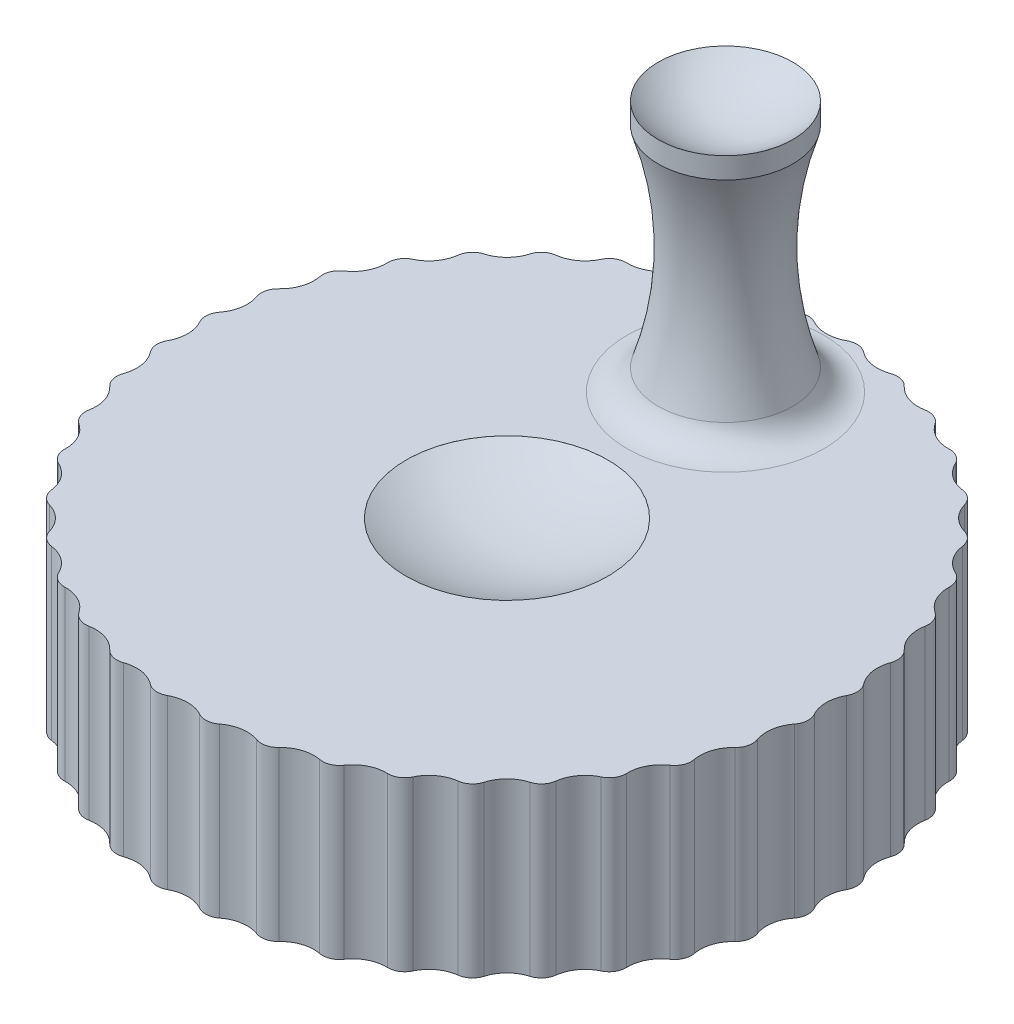
SolidWorks part; units mm, degrees
ref_plane "Front Plane" through (0, 0, 0) normal (0, 0, 1) x (1, 0, 0)
ref_plane "Top Plane" through (0, 0, 0) normal (0, 1, 0) x (1, 0, 0)
ref_plane "Right Plane" through (0, 0, 0) normal (1, 0, 0) x (0, 0, -1)
sketch "Sketch1" plane through (0, 0, 0) normal (0, 1, 0) x (1, 0, 0)
  circle A0 centre (0, 0) radius 20
  dimension "D1" = 40
extrude "Boss-Extrude1" add sketch "Sketch1" along normal blind 10
sketch "Sketch2" plane through (0, 10, 0) normal (0, 1, 0) x (1, 0, 0)
  arc A0 (-1.5536, 19.7405) -> (1.5536, 19.7405) centre (0, 21) ccw
  arc A1 (1.5536, 19.7405) -> (4.6226, 19.2544) centre (3.2851, 20.7415) ccw
  arc A2 (4.6226, 19.2544) -> (7.5777, 18.2943) centre (6.4894, 19.9722) ccw
  arc A3 (7.5777, 18.2943) -> (10.3463, 16.8836) centre (9.5338, 18.7111) ccw
  arc A4 (10.3463, 16.8836) -> (12.8601, 15.0572) centre (12.3435, 16.9894) ccw
  arc A5 (12.8601, 15.0572) -> (15.0572, 12.8601) centre (14.8492, 14.8492) ccw
  arc A6 (15.0572, 12.8601) -> (16.8836, 10.3463) centre (16.9894, 12.3435) ccw
  arc A7 (16.8836, 10.3463) -> (18.2943, 7.5777) centre (18.7111, 9.5338) ccw
  arc A8 (18.2943, 7.5777) -> (19.2544, 4.6226) centre (19.9722, 6.4894) ccw
  arc A9 (19.2544, 4.6226) -> (19.7405, 1.5536) centre (20.7415, 3.2851) ccw
  arc A10 (19.7405, 1.5536) -> (19.7405, -1.5536) centre (21, 0) ccw
  arc A11 (19.7405, -1.5536) -> (19.2544, -4.6226) centre (20.7415, -3.2851) ccw
  arc A12 (19.2544, -4.6226) -> (18.2943, -7.5777) centre (19.9722, -6.4894) ccw
  arc A13 (18.2943, -7.5777) -> (16.8836, -10.3463) centre (18.7111, -9.5338) ccw
  arc A14 (16.8836, -10.3463) -> (15.0572, -12.8601) centre (16.9894, -12.3435) ccw
  arc A15 (15.0572, -12.8601) -> (12.8601, -15.0572) centre (14.8492, -14.8492) ccw
  arc A16 (11.531, -18.8169) -> (14.3326, -16.7814) centre (12.3435, -16.9894) ccw
  arc A17 (8.4454, -20.3891) -> (11.531, -18.8169) centre (9.5338, -18.7111) ccw
  arc A18 (5.1519, -21.4592) -> (8.4454, -20.3891) centre (6.4894, -19.9722) ccw
  arc A19 (1.7315, -22.0009) -> (5.1519, -21.4592) centre (3.2851, -20.7415) ccw
  arc A20 (-1.7315, -22.0009) -> (1.7315, -22.0009) centre (0, -21) ccw
  arc A21 (-5.1519, -21.4592) -> (-1.7315, -22.0009) centre (-3.2851, -20.7415) ccw
  arc A22 (-8.4454, -20.3891) -> (-5.1519, -21.4592) centre (-6.4894, -19.9722) ccw
  arc A23 (-11.531, -18.8169) -> (-8.4454, -20.3891) centre (-9.5338, -18.7111) ccw
  arc A24 (-14.3326, -16.7814) -> (-11.531, -18.8169) centre (-12.3435, -16.9894) ccw
  arc A25 (-16.7814, -14.3326) -> (-14.3326, -16.7814) centre (-14.8492, -14.8492) ccw
  arc A26 (-18.8169, -11.531) -> (-16.7814, -14.3326) centre (-16.9894, -12.3435) ccw
  arc A27 (-20.3891, -8.4454) -> (-18.8169, -11.531) centre (-18.7111, -9.5338) ccw
  arc A28 (-21.4592, -5.1519) -> (-20.3891, -8.4454) centre (-19.9722, -6.4894) ccw
  arc A29 (-22.0009, -1.7315) -> (-21.4592, -5.1519) centre (-20.7415, -3.2851) ccw
  arc A30 (-22.0009, 1.7315) -> (-22.0009, -1.7315) centre (-21, 0) ccw
  arc A31 (-21.4592, 5.1519) -> (-22.0009, 1.7315) centre (-20.7415, 3.2851) ccw
  arc A32 (-20.3891, 8.4454) -> (-21.4592, 5.1519) centre (-19.9722, 6.4894) ccw
  arc A33 (-18.8169, 11.531) -> (-20.3891, 8.4454) centre (-18.7111, 9.5338) ccw
  arc A34 (-16.7814, 14.3326) -> (-18.8169, 11.531) centre (-16.9894, 12.3435) ccw
  arc A35 (-15.0572, 12.8601) -> (-12.8601, 15.0572) centre (-14.8492, 14.8492) ccw
  arc A36 (-12.8601, 15.0572) -> (-10.3463, 16.8836) centre (-12.3435, 16.9894) ccw
  arc A37 (-10.3463, 16.8836) -> (-7.5777, 18.2943) centre (-9.5338, 18.7111) ccw
  arc A38 (-7.5777, 18.2943) -> (-4.6226, 19.2544) centre (-6.4894, 19.9722) ccw
  arc A39 (-4.6226, 19.2544) -> (-1.5536, 19.7405) centre (-3.2851, 20.7415) ccw
  arc A40 (-14.3326, 16.7814) -> (-16.7814, 14.3326) centre (-14.8492, 14.8492) ccw
  arc A41 (-11.531, 18.8169) -> (-14.3326, 16.7814) centre (-12.3435, 16.9894) ccw
  arc A42 (-8.4454, 20.3891) -> (-11.531, 18.8169) centre (-9.5338, 18.7111) ccw
  arc A43 (-5.1519, 21.4592) -> (-8.4454, 20.3891) centre (-6.4894, 19.9722) ccw
  arc A44 (-1.7315, 22.0009) -> (-5.1519, 21.4592) centre (-3.2851, 20.7415) ccw
  arc A45 (1.7315, 22.0009) -> (-1.7315, 22.0009) centre (0, 21) ccw
  arc A46 (5.1519, 21.4592) -> (1.7315, 22.0009) centre (3.2851, 20.7415) ccw
  arc A47 (8.4454, 20.3891) -> (5.1519, 21.4592) centre (6.4894, 19.9722) ccw
  arc A48 (11.531, 18.8169) -> (8.4454, 20.3891) centre (9.5338, 18.7111) ccw
  arc A49 (14.3326, 16.7814) -> (11.531, 18.8169) centre (12.3435, 16.9894) ccw
  arc A50 (16.7814, 14.3326) -> (14.3326, 16.7814) centre (14.8492, 14.8492) ccw
  arc A51 (18.8169, 11.531) -> (16.7814, 14.3326) centre (16.9894, 12.3435) ccw
  arc A52 (20.3891, 8.4454) -> (18.8169, 11.531) centre (18.7111, 9.5338) ccw
  arc A53 (21.4592, 5.1519) -> (20.3891, 8.4454) centre (19.9722, 6.4894) ccw
  arc A54 (22.0009, 1.7315) -> (21.4592, 5.1519) centre (20.7415, 3.2851) ccw
  arc A55 (22.0009, -1.7315) -> (22.0009, 1.7315) centre (21, 0) ccw
  arc A56 (21.4592, -5.1519) -> (22.0009, -1.7315) centre (20.7415, -3.2851) ccw
  arc A57 (20.3891, -8.4454) -> (21.4592, -5.1519) centre (19.9722, -6.4894) ccw
  arc A58 (18.8169, -11.531) -> (20.3891, -8.4454) centre (18.7111, -9.5338) ccw
  arc A59 (16.7814, -14.3326) -> (18.8169, -11.531) centre (16.9894, -12.3435) ccw
  arc A60 (-16.8836, 10.3463) -> (-15.0572, 12.8601) centre (-16.9894, 12.3435) ccw
  arc A61 (-18.2943, 7.5777) -> (-16.8836, 10.3463) centre (-18.7111, 9.5338) ccw
  arc A62 (-19.2544, 4.6226) -> (-18.2943, 7.5777) centre (-19.9722, 6.4894) ccw
  arc A63 (-19.7405, 1.5536) -> (-19.2544, 4.6226) centre (-20.7415, 3.2851) ccw
  arc A64 (-19.7405, -1.5536) -> (-19.7405, 1.5536) centre (-21, 0) ccw
  arc A65 (-19.2544, -4.6226) -> (-19.7405, -1.5536) centre (-20.7415, -3.2851) ccw
  arc A66 (-18.2943, -7.5777) -> (-19.2544, -4.6226) centre (-19.9722, -6.4894) ccw
  arc A67 (-16.8836, -10.3463) -> (-18.2943, -7.5777) centre (-18.7111, -9.5338) ccw
  arc A68 (-15.0572, -12.8601) -> (-16.8836, -10.3463) centre (-16.9894, -12.3435) ccw
  arc A69 (-12.8601, -15.0572) -> (-15.0572, -12.8601) centre (-14.8492, -14.8492) ccw
  arc A70 (-10.3463, -16.8836) -> (-12.8601, -15.0572) centre (-12.3435, -16.9894) ccw
  arc A71 (-7.5777, -18.2943) -> (-10.3463, -16.8836) centre (-9.5338, -18.7111) ccw
  arc A72 (-4.6226, -19.2544) -> (-7.5777, -18.2943) centre (-6.4894, -19.9722) ccw
  arc A73 (-1.5536, -19.7405) -> (-4.6226, -19.2544) centre (-3.2851, -20.7415) ccw
  arc A74 (1.5536, -19.7405) -> (-1.5536, -19.7405) centre (0, -21) ccw
  arc A75 (4.6226, -19.2544) -> (1.5536, -19.7405) centre (3.2851, -20.7415) ccw
  arc A76 (7.5777, -18.2943) -> (4.6226, -19.2544) centre (6.4894, -19.9722) ccw
  arc A77 (10.3463, -16.8836) -> (7.5777, -18.2943) centre (9.5338, -18.7111) ccw
  arc A78 (14.3326, -16.7814) -> (16.7814, -14.3326) centre (14.8492, -14.8492) ccw
  arc A79 (12.8601, -15.0572) -> (10.3463, -16.8836) centre (12.3435, -16.9894) ccw
  point P64 (0, 0)
  dimension "D2" = 4
  dimension "D1" = 21
  dimension "D3" = 40
extrude "Cut-Extrude1" cut sketch "Sketch2" against normal through all both and the other way through all
fillet "Fillet2" radius 1 40 edges at (10.3463, 5, -16.8836) (7.5777, 5, -18.2943) (4.6226, 5, -19.2544) (1.5536, 5, -19.7405) (-1.5536, 5, -19.7405) (-4.6226, 5, -19.2544) (-7.5777, 5, -18.2943) (-12.8601, 5, -15.0572) (-15.0572, 5, -12.8601) (-16.8836, 5, -10.3463) (-18.2943, 5, -7.5777) (-19.2544, 5, -4.6226) (-19.7405, 5, -1.5536) (-19.7405, 5, 1.5536) (-19.2544, 5, 4.6226) (-16.8836, 5, 10.3463) (-15.0572, 5, 12.8601) (-12.8601, 5, 15.0572) (-7.5777, 5, 18.2943) (-1.5536, 5, 19.7405) (-4.6226, 5, 19.2544) (1.5536, 5, 19.7405) (4.6226, 5, 19.2544) (10.3463, 5, 16.8836) (12.8601, 5, 15.0572) (15.0572, 5, 12.8601) (16.8836, 5, 10.3463) (19.2544, 5, 4.6226) (19.7405, 5, -1.5536) (19.2544, 5, -4.6226) (18.2943, 5, -7.5777) (15.0572, 5, -12.8601)
sketch "Sketch4" plane through (0, 10, 0) normal (0, 1, 0) x (1, 0, 0)
  circle A0 centre (0, 0) radius 6
  dimension "D1" = 12
extrude "Cut-Extrude3" cut sketch "Sketch4" against normal blind 0.001
dome "Dome2" faces to dome 1 distance 1.5 reverse direction yes elliptical dome no face at (0, 9.999, 6) parameters "D1"=1.5
sketch "Sketch5" plane through (0, 10, 0) normal (0, 1, 0) x (1, 0, 0)
  circle A0 centre (0, 13) radius 4
  dimension "D1" = 8
  dimension "D2" = 13
extrude "Boss-Extrude2" add sketch "Sketch5" along normal blind 15
sketch "Sketch6" plane through (0, 25, 0) normal (0, 1, 0) x (1, 0, 0)
  point P0 (0, 13)
ref_plane "Plane1" through (0, 0, -13) normal (0, 0, 1) x (1, 0, 0)
sketch "Sketch7" plane through (0, 0, -13) normal (0, 0, 1) x (1, 0, 0)
  line L0 (0, 25) -> (0, 10) construction
  line L1 (4, 10) -> (-4, 10) construction
  line L2 (-4, 23.745) -> (-4, 11.255)
  line L3 (-4, 25) -> (-4, 10) construction
  arc A2 (-4, 23.745) -> (-4, 11.255) centre (-23, 17.5) cw
  point P5 (-3, 17.5)
  dimension "D2" = 20
  dimension "D1" = 1
  dimension "D3" = 7.5
revolve "Cut-Revolve1" cut sketch "Sketch7" angle 360 about L0
fillet "Fillet3" radius 2 1 edges at (0, 10, -9)
dome "Dome3" faces to dome 1 distance 1.5 reverse direction yes elliptical dome no face at (0, 25, -9) parameters "D1"=1.5
sketch "Sketch9" plane through (0, 0, 0) normal (0, -1, 0) x (1, 0, 0)
  circle A0 centre (0, 0) radius 2.75
  dimension "D1" = 5.5
extrude "Cut-Extrude4" cut sketch "Sketch9" against normal blind 7.5
chamfer "Chamfer1" distance 2 angle 20 1 edges at (0, 0, -2.75) first distance on face at (0, 0, -2.75)
